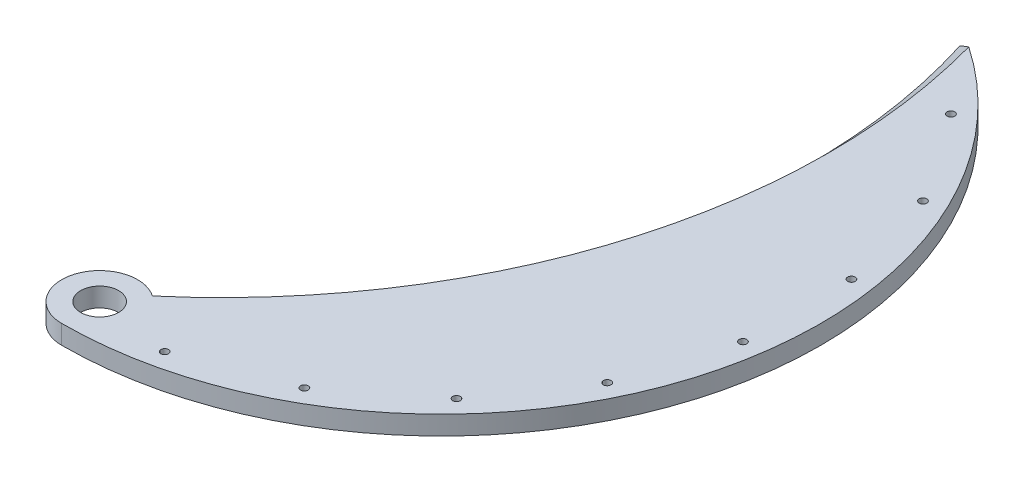
SolidWorks part; units mm, degrees
ref_plane "Ön Düzlem" through (0, 0, 0) normal (0, 0, 1) x (1, 0, 0)
ref_plane "Üst Düzlem" through (0, 0, 0) normal (0, 1, 0) x (1, 0, 0)
ref_plane "Sağ Düzlem" through (0, 0, 0) normal (1, 0, 0) x (0, 0, -1)
sketch "Çizim1" plane through (0, 0, 0) normal (0, 1, 0) x (1, 0, 0)
  line L0 (0, 90) -> (50, 176.6025) construction
  line L2 (0, 0) -> (0, 90) construction
  circle A0 centre (0, 0) radius 50 construction
  circle A1 centre (0, 90) radius 100 construction
  arc A2 (50, 176.6025) -> (-1.708, -9.9854) centre (0, 90) cw
  circle A4 centre (0, 0) radius 10
  circle A5 centre (0, 0) radius 5
  arc A7 (0, 10) -> (50, 176.6025) centre (-97.8852, 130.181) ccw
  dimension "D1" = 100
  dimension "D3" = 200
  dimension "D4" = 20
  dimension "D5" = 10
  dimension "D6" = 155
  dimension "D2" = 150
extrude "Yükseklik-Ekstrüzyon1" add sketch "Çizim1" along normal blind 5 contours A4 A5 | A7 A4 A2 region at (61.2734, 0, -69.7424) region at (-9.7172, 0, 0)
chamfer "Pah1" distance 5 angle 45 1 edges at (50.5731, 5, -85.6264)
sketch "Çizim2" plane through (0, 5, 0) normal (0, 1, 0) x (1, 0, 0)
  arc A0 (69.3485, 154.9291) -> (0, -5) centre (0, 90) cw construction
  arc A1 (0, -10) -> (56.3944, 172.5813) centre (0, 90) ccw construction
  circle A2 centre (0, 0) radius 5 construction
  circle A3 centre (69.3485, 154.9291) radius 1
  circle A4 centre (85.5053, 131.3987) radius 1
  circle A5 centre (93.9431, 104.1311) radius 1
  circle A6 centre (93.9004, 75.5879) radius 1
  circle A7 centre (85.381, 48.3457) radius 1
  circle A8 centre (69.154, 24.8638) radius 1
  circle A9 centre (46.6842, 7.2619) radius 1
  circle A10 centre (20, -2.8709) radius 1
  point P25 (0, 90)
  dimension "D1" = 5
  dimension "D2" = 2
  dimension "D3" = 20
extrude "kanca delikleri" cut sketch "Çizim2" against normal through all
